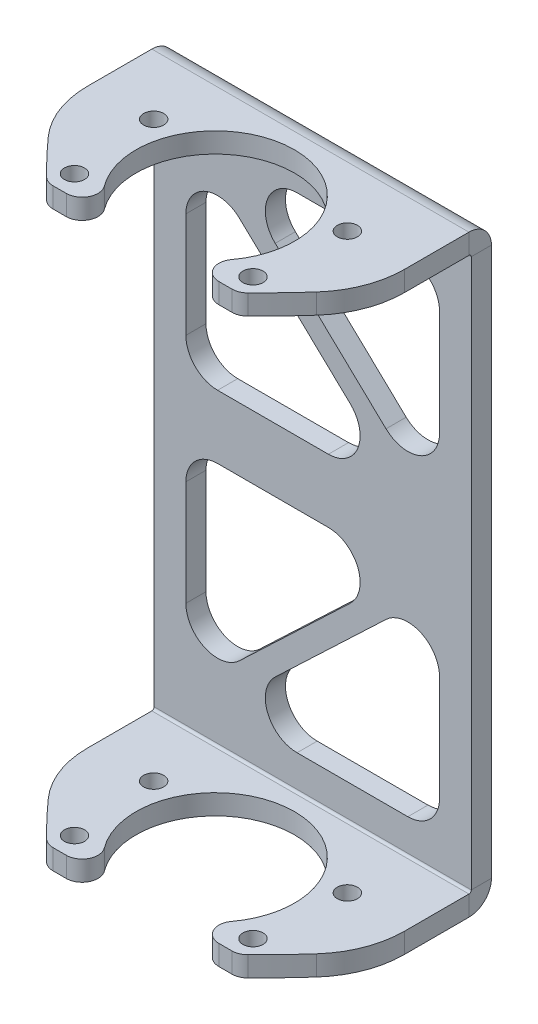
SolidWorks part; units mm, degrees
note: The reader was unsure of these and kept them because the rebuilt part matched: flange length of "Edge-Flange2", "Edge-Flange3".
material "Plain Carbon Steel"
ref_plane "Front Plane" through (0, 0, 0) normal (0, 0, 1) x (1, 0, 0)
ref_plane "Top Plane" through (0, 0, 0) normal (0, 1, 0) x (1, 0, 0)
ref_plane "Right Plane" through (0, 0, 0) normal (1, 0, 0) x (0, 0, -1)
sketch "Sketch1" plane through (0, 0, 0) normal (0, 1, 0) x (1, 0, 0)
  line L1 (-50, 30) -> (50, 30)
  line L2 (-50, 30) -> (-50, -30)
  line L3 (-50, -30) -> (50, -30)
  line L4 (50, 30) -> (50, -30)
  line L5 (-50, 30) -> (50, -30) construction
  line L6 (-50, -30) -> (50, 30) construction
  point P0 (0, 0)
  dimension "D1" = 60
  dimension "D2" = 100
base flange "Base-Flange1" sketch "Sketch1" thickness 6.35 reverse thickness direction no parameters "D1"=0.7366
edge flange "Edge-Flange2" sketch "Sketch24" flange angle 90 flange length 187.1 flange position material inside bend radius 0.7366 thickness 6.35 parameters "D6"=10
bend "EdgeBend4" bend radius 0.7366 bend angle 90 parameters "D5"=1
sketch "Sketch24" plane through (0, -6.35, -30) normal (0, 0, 1) x (-1, 0, 0)
  line L1 (50, 0) -> (-50, 0) construction
  line L2 (-50, 0) -> (-50, 180.75)
  line L3 (-50, 180.75) -> (50, 180.75)
  line L4 (50, 180.75) -> (50, 0)
  line L5 (50, 0) -> (-50, 0)
edge flange "Edge-Flange3" sketch "Sketch26" flange angle 90 flange length 60 flange position material inside bend radius 0.7366 thickness 6.35 parameters "D6"=10
bend "EdgeBend5" bend radius 0.7366 bend angle 90 parameters "D5"=2
sketch "Sketch26" plane through (0, -187.1, -23.65) normal (0, 1, 0) x (-1, 0, 0)
  line L1 (50, 0) -> (-50, 0) construction
  line L2 (-50, 0) -> (-50, 53.65)
  line L3 (-50, 53.65) -> (50, 53.65)
  line L4 (50, 53.65) -> (50, 0)
  line L5 (50, 0) -> (-50, 0)
sketch "Sketch27" plane through (0, -187.1, 0) normal (0, -1, 0) x (1, 0, 0)
  line L0 (-50, -22.9134) -> (50, -22.9134) construction
  circle A1 centre (0, 7.0866) radius 25
  dimension "D1" = 30
  dimension "D2" = 50
extrude "Cut-Extrude2" cut sketch "Sketch27" against normal through all
fillet "Fillet3" radius 5 8 edges at (-50, -3.175, 30) (-9.9988, -3.175, 30) (9.9988, -3.175, 30) (50, -3.175, 30) (-50, -183.925, 30) (50, -183.925, 30) (-9.9988, -183.925, 30) (9.9988, -183.925, 30)
sketch "Sketch28" plane through (0, 0, 0) normal (0, 1, 0) x (1, 0, 0)
  line L0 (0, 25.4134) -> (0, -39.5866) construction
  line L1 (0, -7.0866) -> (-30.54, 4.0291) construction
  line L2 (-32.5, -7.0866) -> (32.5, -7.0866) construction
  line L3 (0, -7.0866) -> (30.54, 4.0291) construction
  line L4 (0, -7.0866) -> (-28.1458, -23.3366) construction
  line L6 (0, -7.0866) -> (28.1458, -23.3366) construction
  circle A0 centre (0, -7.0866) radius 32.5 construction
  arc A1 (20.0539, -22.0144) -> (-20.0539, -22.0144) centre (0, -7.0866) ccw construction
  point P7 (-32.5, -7.0866)
  point P8 (-30.54, 4.0291)
  point P11 (30.54, 4.0291)
  point P12 (32.5, -7.0866)
  point P15 (-28.1458, -23.3366)
  point P18 (28.1458, -23.3366)
  dimension "D1" = 65
  dimension "D2" = 20
  dimension "D3" = 30
hole_wizard "1/4 (0.25) Diameter Hole1" positions "Sketch28" profile "Sketch29" hole size "1/4" standard "ANSI Inch"
sketch "Sketch29" plane through (28.1458, 0, 23.3366) normal (1, 0, 0) x (0, 0, 1)
  line L0 (0, 0) -> (0, 187.1)
  line L1 (0, 187.1) -> (3.175, 187.1)
  line L2 (3.175, 187.1) -> (3.175, 0)
  line L5 (3.175, 0) -> (0, 0)
  line L11 (0, -6.35) -> (0, 107.95) construction
  dimension "Thru Hole Dia." = 6.35
  dimension "Thru Hole Depth" = 187.1
sketch "Sketch30" plane through (0, 0, -30) normal (0, 0, -1) x (-1, 0, 0)
  line L0 (-50, -93.55) -> (50, -93.55) construction
  line L1 (50, -7.0866) -> (50, -180.0134) construction
  line L2 (-50, -180.0134) -> (-50, -7.0866) construction
  line L3 (-40, -27.0866) -> (-40, -60.2657)
  line L4 (-23.1145, -67.5176) -> (11.8301, -34.3385)
  line L5 (4.9446, -17.0866) -> (-30, -17.0866)
  line L6 (50, -7.0866) -> (-50, -7.0866) construction
  line L7 (23.1145, -33.119) -> (-11.8301, -66.2981)
  line L8 (-4.9446, -83.55) -> (30, -83.55)
  line L9 (40, -73.55) -> (40, -40.3709)
  line L10 (-23.1145, -119.5824) -> (11.8301, -152.7615)
  line L11 (-40, -160.0134) -> (-40, -126.8343)
  line L12 (4.9446, -170.0134) -> (-30, -170.0134)
  line L13 (-4.9446, -103.55) -> (30, -103.55)
  line L14 (23.1145, -153.981) -> (-11.8301, -120.8019)
  line L15 (40, -113.55) -> (40, -146.7291)
  arc A0 (-40, -60.2657) -> (-23.1145, -67.5176) centre (-30, -60.2657) ccw
  arc A1 (11.8301, -34.3385) -> (4.9446, -17.0866) centre (4.9446, -27.0866) ccw
  arc A2 (-40, -27.0866) -> (-30, -17.0866) centre (-30, -27.0866) cw
  arc A3 (30, -83.55) -> (40, -73.55) centre (30, -73.55) ccw
  arc A4 (-11.8301, -66.2981) -> (-4.9446, -83.55) centre (-4.9446, -73.55) ccw
  arc A5 (23.1145, -33.119) -> (40, -40.3709) centre (30, -40.3709) cw
  arc A6 (-40, -126.8343) -> (-23.1145, -119.5824) centre (-30, -126.8343) cw
  arc A7 (11.8301, -152.7615) -> (4.9446, -170.0134) centre (4.9446, -160.0134) cw
  arc A8 (-40, -160.0134) -> (-30, -170.0134) centre (-30, -160.0134) ccw
  arc A9 (-11.8301, -120.8019) -> (-4.9446, -103.55) centre (-4.9446, -113.55) cw
  arc A10 (30, -103.55) -> (40, -113.55) centre (30, -113.55) cw
  arc A11 (23.1145, -153.981) -> (40, -146.7291) centre (30, -146.7291) ccw
  point P16 (-40, -83.55)
  point P19 (30, -17.0866)
  point P28 (40, -17.0866)
  dimension "D7" = 10
  dimension "D1" = 10
  dimension "D2" = 10
  dimension "D3" = 10
  dimension "D4" = 20
  dimension "D5" = 10
  dimension "D6" = 20
extrude "Cut-Extrude3" cut sketch "Sketch30" against normal through all
sketch "Sketch31" plane through (0, -187.1, 0) normal (0, -1, 0) x (1, 0, 0)
  line L0 (30.2464, 30) -> (50, 30)
  line L1 (50, 30) -> (50, 8.4861)
  line L4 (0, 0) -> (0, 79.9562) construction
  line L7 (-50, -22.9134) -> (-50, 25) construction
  line L8 (50, 25) -> (50, -22.9134) construction
  line L9 (24.0647, 30) -> (45, 30) construction
  line L10 (-30.2464, 30) -> (-50, 30)
  line L11 (-50, 30) -> (-50, 8.4861)
  arc A1 (30.2464, 30) -> (50, 8.4861) centre (-151.0901, -156.3251) cw
  arc A3 (107.5508, -129.7762) -> (27.4709, 32.6615) centre (-151.0901, -156.3251) ccw construction
  arc A5 (-30.2464, 30) -> (-50, 8.4861) centre (151.0901, -156.3251) ccw
  dimension "D1" = 47.9134
extrude "Cut-Extrude4" cut sketch "Sketch31" against normal through all
fillet "Fillet4" radius 30 4 edges at (50, -183.925, 8.4861) (-50, -183.925, 8.4861) (-50, -3.175, 8.4861) (50, -3.175, 8.4861)
fillet "Fillet5" radius 5 4 edges at (30.2464, -183.925, 30) (-30.2464, -183.925, 30) (-30.2464, -3.175, 30) (30.2464, -3.175, 30)
sketch "Bend-Lines1" [suppressed] plane through (0, 0, 0) normal (0, 1, 0) x (1, 0, 0)
sketch "Bounding-Box1" [suppressed] plane through (0, 0, 0) normal (0, 1, 0) x (1, 0, 0)
sheet metal parameters "Sheet-Metal1" thickness 6.35 parameters "D1"=0.7366
flat pattern "Flat-Pattern1" [suppressed]
sketch "Bend-Lines2" plane through (0, 0, 0) normal (0, 1, 0) x (1, 0, 0)
sketch3d "Bounding-Box2" [suppressed]
  line L0 (30, -10, 0) -> (-30, -10, 0) construction
  line L1 (30, 10, 0) -> (-30, 10, 0) construction
  line L2 (30, -10, 0) -> (30, 10, 0) construction
  line L3 (-30, -10, 0) -> (-30, 10, 0) construction
sheet metal parameters "Sheet-Metal3" thickness 6.35 parameters "D1"=0.7366
flat pattern "Flat-Pattern1"
sketch "Bend-Lines2" plane through (0, 0, 0) normal (0, 1, 0) x (1, 0, 0)
  line L2 (50, 25.9856) -> (-50, 25.9856) construction
  line L3 (50, 25.9856) -> (-50, 25.9856) construction
  point P0 (30, 5.9856)
  point P1 (-30, 5.9856)
sketch3d "Bounding-Box2" [suppressed]
  line L0 (-50, 204.7211, 0) -> (-50, -30, 0) construction
  line L1 (50, 204.7211, 0) -> (50, -30, 0) construction
  line L2 (-50, 204.7211, 0) -> (50, 204.7211, 0) construction
  line L3 (-50, -30, 0) -> (50, -30, 0) construction
bend of the flat pattern "Flatten-<EdgeBend4>1"
sheet metal parameters "Sheet-Metal4" thickness 6.35 parameters "D1"=0.7366
flat pattern "Flat-Pattern1"
sketch "Bend-Lines2" plane through (0, 0, 0) normal (0, 1, 0) x (1, 0, 0)
  line L4 (50, 200.7067) -> (-50, 200.7067) construction
  line L5 (50, 25.9856) -> (-50, 25.9856) construction
  line L6 (50, 200.7067) -> (-50, 200.7067) construction
  line L7 (50, 25.9856) -> (-50, 25.9856) construction
sketch3d "Bounding-Box2" [suppressed]
  line L0 (-50, 256.6923, 0) -> (-50, -30, 0) construction
  line L1 (50, 256.6923, 0) -> (50, -30, 0) construction
  line L2 (-50, 256.6923, 0) -> (50, 256.6923, 0) construction
  line L3 (-50, -30, 0) -> (50, -30, 0) construction
bend of the flat pattern "Flatten-<EdgeBend4>2"
bend of the flat pattern "Flatten-<EdgeBend5>1"
sheet metal parameters "Sheet-Metal367" thickness 6.35 parameters "D1"=0.7366
flat pattern "Flat-Pattern1"
sketch "Bend-Lines2" plane through (0, 0, 0) normal (0, 1, 0) x (1, 0, 0)
  line L4 (50, 200.7067) -> (-50, 200.7067) construction
  line L5 (50, 25.9856) -> (-50, 25.9856) construction
  line L6 (50, 200.7067) -> (-50, 200.7067) construction
  line L7 (50, 25.9856) -> (-50, 25.9856) construction
sketch3d "Bounding-Box2" [suppressed]
  line L0 (50, 256.6922, 0) -> (50, -30, 0) construction
  line L1 (-50, 256.6923, 0) -> (-50, -30, 0) construction
  line L2 (50, 256.6922, 0) -> (-50, 256.6923, 0) construction
  line L3 (50, -30, 0) -> (-50, -30, 0) construction
bend of the flat pattern "Flatten-<EdgeBend4>2"
bend of the flat pattern "Flatten-<EdgeBend5>1"
sheet metal parameters "Sheet-Metal368" thickness 6.35 parameters "D1"=0.7366
flat pattern "Flat-Pattern1"
sketch "Bend-Lines2" plane through (0, 0, 0) normal (0, 1, 0) x (1, 0, 0)
  line L4 (50, 204.0567) -> (-50, 204.0567) construction
  line L5 (50, 25.9856) -> (-50, 25.9856) construction
  line L6 (50, 204.0567) -> (-50, 204.0567) construction
  line L7 (50, 25.9856) -> (-50, 25.9856) construction
sketch3d "Bounding-Box2" [suppressed]
  line L0 (50, 260.0422, 0) -> (50, -30, 0) construction
  line L1 (-50, 260.0423, 0) -> (-50, -30, 0) construction
  line L2 (50, 260.0422, 0) -> (-50, 260.0423, 0) construction
  line L3 (50, -30, 0) -> (-50, -30, 0) construction
bend of the flat pattern "Flatten-<EdgeBend4>2"
bend of the flat pattern "Flatten-<EdgeBend5>1"
sheet metal parameters "Sheet-Metal369" thickness 6.35 parameters "D1"=0.7366
flat pattern "Flat-Pattern1"
sketch "Bend-Lines2" plane through (0, 0, 0) normal (0, 1, 0) x (1, 0, 0)
  line L4 (50, 205.0567) -> (-50, 205.0567) construction
  line L5 (50, 25.9856) -> (-50, 25.9856) construction
  line L6 (50, 205.0567) -> (-50, 205.0567) construction
  line L7 (50, 25.9856) -> (-50, 25.9856) construction
sketch3d "Bounding-Box2" [suppressed]
  line L0 (50, 261.0422, 0) -> (50, -30, 0) construction
  line L1 (-50, 261.0423, 0) -> (-50, -30, 0) construction
  line L2 (50, 261.0422, 0) -> (-50, 261.0423, 0) construction
  line L3 (50, -30, 0) -> (-50, -30, 0) construction
bend of the flat pattern "Flatten-<EdgeBend4>2"
bend of the flat pattern "Flatten-<EdgeBend5>1"
sheet metal parameters "Sheet-Metal464" thickness 6.35 parameters "D1"=0.7366
flat pattern "Flat-Pattern1"
sketch "Bend-Lines2" plane through (0, 0, 0) normal (0, 1, 0) x (1, 0, 0)
  line L4 (50, 205.0567) -> (-50, 205.0567) construction
  line L5 (50, 25.9856) -> (-50, 25.9856) construction
  line L6 (50, 205.0567) -> (-50, 205.0567) construction
  line L7 (50, 25.9856) -> (-50, 25.9856) construction
sketch3d "Bounding-Box2" [suppressed]
  line L0 (50, 261.0423, 0) -> (50, -30, 0) construction
  line L1 (-50, 261.0423, 0) -> (-50, -30, 0) construction
  line L2 (50, 261.0423, 0) -> (-50, 261.0423, 0) construction
  line L3 (50, -30, 0) -> (-50, -30, 0) construction
bend of the flat pattern "Flatten-<EdgeBend4>2"
bend of the flat pattern "Flatten-<EdgeBend5>1"
